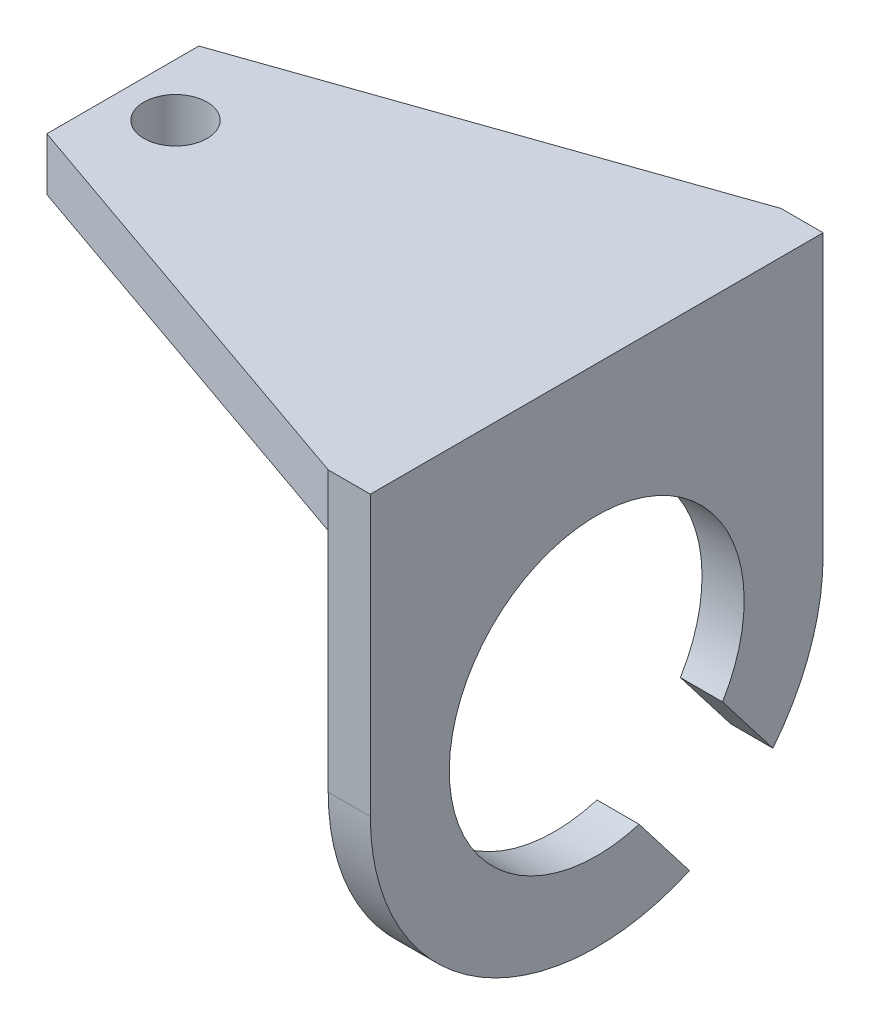
SolidWorks part; units mm, degrees
ref_plane "Front Plane" through (0, 0, 0) normal (0, 0, 1) x (1, 0, 0)
ref_plane "Top Plane" through (0, 0, 0) normal (0, 1, 0) x (1, 0, 0)
ref_plane "Right Plane" through (0, 0, 0) normal (1, 0, 0) x (0, 0, -1)
sketch "Sketch1" plane through (0, 0, 0) normal (1, 0, 0) x (0, 0, -1)
  circle A0 centre (0, 0) radius 14
  circle A1 centre (0, 0) radius 21.5
  dimension "D1" = 28
  dimension "D2" = 7.5
extrude "Boss-Extrude1" add sketch "Sketch1" along normal blind 4
ref_plane "Plane1" through (0, 21.5, 0) normal (0, 1, 0) x (1, 0, 0)
sketch "Sketch2" plane through (0, 21.5, 0) normal (0, 1, 0) x (1, 0, 0)
  line L0 (4, -21.5) -> (4, 21.5) construction
  line L1 (4, -21.5) -> (4, 21.5)
  line L2 (0, 21.5) -> (0, -21.5) construction
  line L3 (0, 21.5) -> (0, -21.5)
  line L4 (4, -21.5) -> (-41, -21.5)
  line L5 (-41, -21.5) -> (-41, 21.5)
  line L6 (-41, 21.5) -> (4, 21.5)
  line L7 (-36, 0) -> (-42.2528, 0) construction
  circle A1 centre (-36, 0) radius 3
  dimension "D2" = 6
  dimension "D4" = 2
  dimension "D1" = 45
extrude "Boss-Extrude2" add sketch "Sketch2" against normal up to surface (21.5 mm away) contours L6 L3 L4 L1 region at (2, 21.5, 0) up to face at (4, 0, -21.5)
extrude "Boss-Extrude3" add sketch "Sketch2<3>" along normal blind 5 contours L6 L5 L4 L3 | L6 L3 L4 L1 | A1 L5 L4 | A1 L6 L5 | L6 | L4 region at (2, 21.5, 0) region at (-20.2474, 21.5, 0)
sketch "Sketch2<3>" plane through (0, 21.5, 0) normal (0, 1, 0) x (1, 0, 0) same geometry as "Sketch2"
ref_point "Point1"
sketch "Sketch3" plane through (0, 21.5, 0) normal (0, -1, 0) x (1, 0, 0)
  line L0 (0, -21.5) -> (-41, -7.216)
  line L1 (-41, 21.5) -> (-41, -21.5) construction
  line L2 (-41, -7.216) -> (-41, 7.216)
  line L3 (-36, 0) -> (-42.2327, 0) construction
  line L4 (0, -21.5) -> (0, 21.5) construction
  line L5 (0, -21.5) -> (0, 21.5)
  line L6 (0, 21.5) -> (-41, 7.216)
  line L7 (0, -21.5) -> (0, -28.4718)
  line L8 (0, -28.4718) -> (-41, -28.4718)
  line L9 (-41, -28.4718) -> (-41, 27.2513)
  line L10 (-41, 27.2513) -> (0, 27.2513)
  line L11 (0, 27.2513) -> (0, 21.5)
  point P12 (-41, 0)
  line M7 (-41, -21.5) -> (0, -21.5)
  line M9 (0, 21.5) -> (-41, 21.5)
  line M10 (-41, 21.5) -> (-41, -21.5)
extrude "Cut-Extrude4" cut sketch "Sketch3" against normal through all contours L2 L3 L9 L8 L7 M7 M10 | L3 L11 L10 L9 M10 M9 | L0 M7 M10 | L6 M9 M10 region at (-27.3333, 21.5, -16.7387) region at (-20.5, 21.5, -24.9859) region at (-20.5, 21.5, 24.3756) region at (-27.3333, 21.5, 16.7387)
sketch "Sketch4" plane through (0, 0, 0) normal (-1, 0, 0) x (0, 0, 1)
  line L0 (-3.9597, 3.053) -> (3.9597, -3.053)
  line L1 (3.9597, -3.053) -> (-14.3585, -26.8111)
  line L2 (-14.3585, -26.8111) -> (-22.2779, -20.705)
  line L3 (-22.2779, -20.705) -> (-3.9597, 3.053)
  line L4 (0, 0) -> (0, -40.6206) construction
  line L5 (0, 0) -> (-25.8301, -33.5007) construction
  point P7 (-29.4363, -28.9493)
  point P9 (-4.4219, -32.6864)
  point P10 (-18.3182, -23.758)
  point P11 (0, 0)
  dimension "D1" = 30
  dimension "D2" = 10
extrude "wire break" cut sketch "Sketch4" against normal through all
